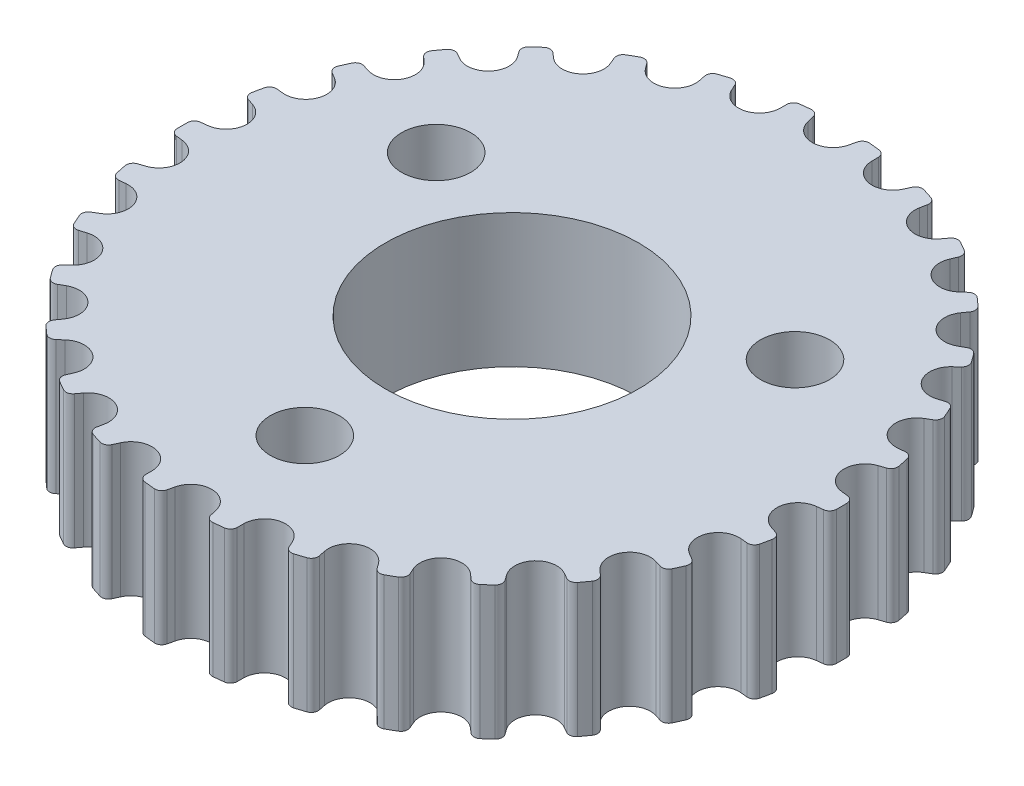
SolidWorks part; units mm, degrees
material "Acrylic (Medium-high impact)"
ref_plane "Front Plane" through (0, 0, 0) normal (0, 0, 1) x (1, 0, 0)
ref_plane "Top Plane" through (0, 0, 0) normal (0, 1, 0) x (1, 0, 0)
ref_plane "Right Plane" through (0, 0, 0) normal (1, 0, 0) x (0, 0, -1)
sketch "Sketch1" plane through (0, 0, 0) normal (0, 1, 0) x (1, 0, 0)
  circle A0 centre (0, 0) radius 14.3239
  dimension "D1" = 28.6479
extrude "Boss-Extrude1" add sketch "Sketch1" along normal blind 5.8
sketch "Sketch2" plane through (0, 5.8, 0) normal (0, 1, 0) x (1, 0, 0)
  line L0 (0, 0) -> (0, 14.3239) construction
  line L1 (-0.8883, 13.7564) -> (-0.95, 14.0339)
  line L2 (-2.9781, 14.0109) -> (-2.9781, 14.3239)
  line L3 (-2.9781, 14.3239) -> (2.9781, 14.3239)
  line L4 (0.8883, 13.7564) -> (0.95, 14.0339)
  line L5 (2.9781, 14.0109) -> (2.9781, 14.3239)
  circle A0 centre (0, 0) radius 14.3239 construction
  arc A1 (0.8883, 13.7564) -> (-0.8883, 13.7564) centre (0, 13.9539) cw
  arc A2 (-0.95, 14.0339) -> (-1.2694, 14.2676) centre (-1.2428, 13.9688) ccw
  arc A4 (0.95, 14.0339) -> (1.2694, 14.2676) centre (1.2428, 13.9688) cw
  arc A5 (-1.2694, 14.2676) -> (-2.9781, 14.0109) centre (0, 0) ccw
  arc A6 (1.2694, 14.2676) -> (2.9781, 14.0109) centre (0, 0) cw
  circle A8 centre (0, 0) radius 14.3239 construction
  point P11 (0, 14.3239)
  point P19 (0, 13.0439)
  dimension "D3" = 0.3
  dimension "D5" = 0.91
  dimension "D2" = 0.95
  dimension "D4" = 1.28
  dimension "D6" = 12
extrude "Cut-Extrude1" cut sketch "Sketch2" against normal through all
pattern_circular "CirPattern1" count 30 over 360 about axis through (0, 5.8, 0) along (0, -1, 0) of "Cut-Extrude1"
sketch "Sketch3" plane through (0, 0, 0) normal (0, -1, 0) x (1, 0, 0)
  circle A0 centre (0, 0) radius 5.5
  dimension "D1" = 11
extrude "Cut-Extrude2" cut sketch "Sketch3" against normal through all
sketch "Sketch4" plane through (0, 0, 0) normal (0, -1, 0) x (1, 0, 0)
  line L0 (0, 0) -> (0, 9) construction
  circle A0 centre (0, 9) radius 1.5
  circle A1 centre (7.7942, -4.5) radius 1.5
  circle A2 centre (-7.7942, -4.5) radius 1.5
  point P14 (0, 0)
  dimension "D1" = 3
  dimension "D2" = 9
  dimension "D3" = 3
extrude "Cut-Extrude3" cut sketch "Sketch4" against normal through all
sketch "Sketch5" plane through (0, 0, 0) normal (0, -1, 0) x (1, 0, 0)
  line L60 (8.7383, -10.682) -> (8.9513, -10.8702)
  line L61 (8.7383, -10.682) -> (8.9513, -10.8702)
  line L62 (9.875, -10.0385) -> (9.7101, -9.807)
  line L63 (9.875, -10.0385) -> (9.7101, -9.807)
  line L64 (12.5987, 6.2896) -> (12.3276, 6.2043)
  line L65 (12.5987, 6.2896) -> (12.3276, 6.2043)
  line L66 (11.5369, 7.5738) -> (11.7463, 7.766)
  line L67 (11.5369, 7.5738) -> (11.7463, 7.766)
  line L68 (-3.638, 13.3126) -> (-3.7561, 13.5712)
  line L69 (-3.638, 13.3126) -> (-3.7561, 13.5712)
  line L70 (-4.9382, 13.1871) -> (-4.8817, 12.9085)
  line L71 (-4.9382, 13.1871) -> (-4.8817, 12.9085)
  line L72 (-11.7463, 7.766) -> (-11.5369, 7.5738)
  line L73 (-11.7463, 7.766) -> (-11.5369, 7.5738)
  line L74 (-12.3276, 6.2043) -> (-12.5987, 6.2896)
  line L75 (-12.3276, 6.2043) -> (-12.5987, 6.2896)
  line L76 (-13.1043, 5.1541) -> (-12.8594, 5.0097)
  line L77 (-13.1043, 5.1541) -> (-12.8594, 5.0097)
  line L78 (-13.3481, 3.5057) -> (-13.6311, 3.5327)
  line L79 (-13.3481, 3.5057) -> (-13.6311, 3.5327)
  line L80 (-13.8895, 2.3169) -> (-13.62, 2.2266)
  line L81 (-13.8895, 2.3169) -> (-13.62, 2.2266)
  line L82 (-13.7853, 0.6538) -> (-14.0677, 0.6215)
  line L83 (-13.7853, 0.6538) -> (-14.0677, 0.6215)
  line L84 (-14.0677, -0.6215) -> (-13.7853, -0.6538)
  line L85 (-14.0677, -0.6215) -> (-13.7853, -0.6538)
  line L86 (-13.62, -2.2266) -> (-13.8895, -2.3169)
  line L87 (-13.62, -2.2266) -> (-13.8895, -2.3169)
  line L88 (-13.6311, -3.5327) -> (-13.3481, -3.5057)
  line L89 (-13.6311, -3.5327) -> (-13.3481, -3.5057)
  line L90 (-12.8594, -5.0097) -> (-13.1043, -5.1541)
  line L91 (-12.8594, -5.0097) -> (-13.1043, -5.1541)
  line L92 (-12.5987, -6.2896) -> (-12.3276, -6.2043)
  line L93 (-12.5987, -6.2896) -> (-12.3276, -6.2043)
  line L94 (-11.5369, -7.5738) -> (-11.7463, -7.766)
  line L95 (-11.5369, -7.5738) -> (-11.7463, -7.766)
  line L96 (-11.0157, -8.7716) -> (-10.7682, -8.6318)
  line L97 (-11.0157, -8.7716) -> (-10.7682, -8.6318)
  line L98 (-9.7101, -9.807) -> (-9.875, -10.0385)
  line L99 (-9.7101, -9.807) -> (-9.875, -10.0385)
  line L100 (-8.9513, -10.8702) -> (-8.7383, -10.682)
  line L101 (-8.9513, -10.8702) -> (-8.7383, -10.682)
  line L102 (-7.4589, -11.6115) -> (-7.5721, -11.8722)
  line L103 (-7.4589, -11.6115) -> (-7.5721, -11.8722)
  line L104 (-6.4956, -12.4937) -> (-6.3264, -12.2653)
  line L105 (-6.4956, -12.4937) -> (-6.3264, -12.2653)
  line L106 (-4.8817, -12.9085) -> (-4.9382, -13.1871)
  line L107 (-4.8817, -12.9085) -> (-4.9382, -13.1871)
  line L108 (-3.7561, -13.5712) -> (-3.638, -13.3126)
  line L109 (-3.7561, -13.5712) -> (-3.638, -13.3126)
  line L110 (-2.0912, -13.6414) -> (-2.0886, -13.9257)
  line L111 (-2.0912, -13.6414) -> (-2.0886, -13.9257)
  line L120 (6.3264, -12.2653) -> (6.4956, -12.4937)
  line L121 (7.5721, -11.8722) -> (7.4589, -11.6115)
  line L124 (10.7682, -8.6318) -> (11.0157, -8.7716)
  line L125 (11.7463, -7.766) -> (11.5369, -7.5738)
  line L126 (12.3276, -6.2043) -> (12.5987, -6.2896)
  line L127 (13.1043, -5.1541) -> (12.8594, -5.0097)
  line L128 (13.3481, -3.5057) -> (13.6311, -3.5327)
  line L129 (13.8895, -2.3169) -> (13.62, -2.2266)
  line L130 (13.7853, -0.6538) -> (14.0677, -0.6215)
  line L131 (14.0677, 0.6215) -> (13.7853, 0.6538)
  line L132 (13.62, 2.2266) -> (13.8895, 2.3169)
  line L133 (13.6311, 3.5327) -> (13.3481, 3.5057)
  line L134 (12.8594, 5.0097) -> (13.1043, 5.1541)
  line L137 (11.0157, 8.7716) -> (10.7682, 8.6318)
  line L138 (9.7101, 9.807) -> (9.875, 10.0385)
  line L139 (8.9513, 10.8702) -> (8.7383, 10.682)
  line L140 (7.4589, 11.6115) -> (7.5721, 11.8722)
  line L141 (6.4956, 12.4937) -> (6.3264, 12.2653)
  line L142 (4.8817, 12.9085) -> (4.9382, 13.1871)
  line L143 (3.7561, 13.5712) -> (3.638, 13.3126)
  line L144 (2.0912, 13.6414) -> (2.0886, 13.9257)
  line L145 (0.8524, 14.0556) -> (0.7907, 13.7781)
  line L146 (-0.7907, 13.7781) -> (-0.8524, 14.0556)
  line L147 (-2.0886, 13.9257) -> (-2.0912, 13.6414)
  line L150 (-6.3264, 12.2653) -> (-6.4956, 12.4937)
  line L151 (-7.5721, 11.8722) -> (-7.4589, 11.6115)
  line L152 (-8.7383, 10.682) -> (-8.9513, 10.8702)
  line L153 (-9.875, 10.0385) -> (-9.7101, 9.807)
  line L154 (-10.7682, 8.6318) -> (-11.0157, 8.7716)
  line L175 (-0.8524, -14.0556) -> (-0.7907, -13.7781)
  line L176 (0.7907, -13.7781) -> (0.8524, -14.0556)
  line L177 (2.0886, -13.9257) -> (2.0912, -13.6414)
  line L178 (3.638, -13.3126) -> (3.7561, -13.5712)
  line L179 (4.9382, -13.1871) -> (4.8817, -12.9085)
  line L180 (6.3264, -12.2653) -> (6.4956, -12.4937)
  line L181 (7.5721, -11.8722) -> (7.4589, -11.6115)
  line L184 (10.7682, -8.6318) -> (11.0157, -8.7716)
  line L185 (11.7463, -7.766) -> (11.5369, -7.5738)
  line L186 (12.3276, -6.2043) -> (12.5987, -6.2896)
  line L187 (13.1043, -5.1541) -> (12.8594, -5.0097)
  line L188 (13.3481, -3.5057) -> (13.6311, -3.5327)
  line L189 (13.8895, -2.3169) -> (13.62, -2.2266)
  line L190 (13.7853, -0.6538) -> (14.0677, -0.6215)
  line L191 (14.0677, 0.6215) -> (13.7853, 0.6538)
  line L192 (13.62, 2.2266) -> (13.8895, 2.3169)
  line L193 (13.6311, 3.5327) -> (13.3481, 3.5057)
  line L194 (12.8594, 5.0097) -> (13.1043, 5.1541)
  line L197 (11.0157, 8.7716) -> (10.7682, 8.6318)
  line L198 (9.7101, 9.807) -> (9.875, 10.0385)
  line L199 (8.9513, 10.8702) -> (8.7383, 10.682)
  line L200 (7.4589, 11.6115) -> (7.5721, 11.8722)
  line L201 (6.4956, 12.4937) -> (6.3264, 12.2653)
  line L202 (4.8817, 12.9085) -> (4.9382, 13.1871)
  line L203 (3.7561, 13.5712) -> (3.638, 13.3126)
  line L204 (2.0912, 13.6414) -> (2.0886, 13.9257)
  line L205 (0.8524, 14.0556) -> (0.7907, 13.7781)
  line L206 (-0.7907, 13.7781) -> (-0.8524, 14.0556)
  line L207 (-2.0886, 13.9257) -> (-2.0912, 13.6414)
  line L210 (-6.3264, 12.2653) -> (-6.4956, 12.4937)
  line L211 (-7.5721, 11.8722) -> (-7.4589, 11.6115)
  line L212 (-8.7383, 10.682) -> (-8.9513, 10.8702)
  line L213 (-9.875, 10.0385) -> (-9.7101, 9.807)
  line L214 (-10.7682, 8.6318) -> (-11.0157, 8.7716)
  line L235 (-0.8524, -14.0556) -> (-0.7907, -13.7781)
  line L236 (0.7907, -13.7781) -> (0.8524, -14.0556)
  line L237 (2.0886, -13.9257) -> (2.0912, -13.6414)
  line L238 (3.638, -13.3126) -> (3.7561, -13.5712)
  line L239 (4.9382, -13.1871) -> (4.8817, -12.9085)
  arc A76 (8.9513, -10.8702) -> (9.479, -10.8719) centre (9.2161, -10.5704) ccw
  arc A77 (8.9513, -10.8702) -> (9.479, -10.8719) centre (9.2161, -10.5704) ccw
  arc A78 (9.479, -10.8719) -> (9.8216, -10.5635) centre (0, 0) ccw
  arc A79 (9.479, -10.8719) -> (9.8216, -10.5635) centre (0, 0) ccw
  arc A80 (9.8216, -10.5635) -> (9.875, -10.0385) centre (9.5492, -10.2705) ccw
  arc A81 (9.8216, -10.5635) -> (9.875, -10.0385) centre (9.5492, -10.2705) ccw
  circle A120 centre (0, 0) radius 13.0439
  arc A121 (-0.8883, 13.7564) -> (0.8883, 13.7564) centre (0, 13.9539) ccw construction
  arc A128 (11.5369, 7.5738) -> (12.3276, 6.2043) centre (12.0845, 6.977) ccw
  arc A129 (11.5369, 7.5738) -> (12.3276, 6.2043) centre (12.0845, 6.977) ccw
  arc A130 (-3.7561, 13.5712) -> (-4.2375, 13.7875) centre (-4.12, 13.4051) ccw
  arc A131 (-3.7561, 13.5712) -> (-4.2375, 13.7875) centre (-4.12, 13.4051) ccw
  arc A132 (-4.2375, 13.7875) -> (-4.6759, 13.645) centre (0, 0) ccw
  arc A133 (-4.2375, 13.7875) -> (-4.6759, 13.645) centre (0, 0) ccw
  arc A134 (-4.6759, 13.645) -> (-4.9382, 13.1871) centre (-4.5462, 13.2666) ccw
  arc A135 (-4.6759, 13.645) -> (-4.9382, 13.1871) centre (-4.5462, 13.2666) ccw
  arc A136 (-11.8032, 8.2906) -> (-11.7463, 7.766) centre (-11.4759, 8.0607) ccw
  arc A137 (-11.8032, 8.2906) -> (-11.7463, 7.766) centre (-11.4759, 8.0607) ccw
  arc A138 (-12.3276, 6.2043) -> (-11.5369, 7.5738) centre (-12.0845, 6.977) ccw
  arc A139 (-12.3276, 6.2043) -> (-11.5369, 7.5738) centre (-12.0845, 6.977) ccw
  arc A140 (-12.5987, 6.2896) -> (-13.0815, 6.0766) centre (-12.7187, 5.908) ccw
  arc A141 (-12.5987, 6.2896) -> (-13.0815, 6.0766) centre (-12.7187, 5.908) ccw
  arc A142 (-13.0815, 6.0766) -> (-13.269, 5.6554) centre (0, 0) ccw
  arc A143 (-13.0815, 6.0766) -> (-13.269, 5.6554) centre (0, 0) ccw
  arc A144 (-13.269, 5.6554) -> (-13.1043, 5.1541) centre (-12.901, 5.4986) ccw
  arc A145 (-13.269, 5.6554) -> (-13.1043, 5.1541) centre (-12.901, 5.4986) ccw
  arc A146 (-13.3481, 3.5057) -> (-12.8594, 5.0097) centre (-13.271, 4.312) ccw
  arc A147 (-13.3481, 3.5057) -> (-12.8594, 5.0097) centre (-13.271, 4.312) ccw
  arc A148 (-13.6311, 3.5327) -> (-14.059, 3.224) centre (-13.6691, 3.1346) ccw
  arc A149 (-13.6311, 3.5327) -> (-14.059, 3.224) centre (-13.6691, 3.1346) ccw
  arc A150 (-14.059, 3.224) -> (-14.1549, 2.7731) centre (0, 0) ccw
  arc A151 (-14.059, 3.224) -> (-14.1549, 2.7731) centre (0, 0) ccw
  arc A152 (-14.1549, 2.7731) -> (-13.8895, 2.3169) centre (-13.7623, 2.6962) ccw
  arc A153 (-14.1549, 2.7731) -> (-13.8895, 2.3169) centre (-13.7623, 2.6962) ccw
  arc A154 (-13.7853, 0.6538) -> (-13.62, 2.2266) centre (-13.8775, 1.4586) ccw
  arc A155 (-13.7853, 0.6538) -> (-13.62, 2.2266) centre (-13.8775, 1.4586) ccw
  arc A156 (-14.0677, 0.6215) -> (-14.4221, 0.2305) centre (-14.0222, 0.2241) ccw
  arc A157 (-14.0677, 0.6215) -> (-14.4221, 0.2305) centre (-14.0222, 0.2241) ccw
  arc A158 (-14.4221, 0.2305) -> (-14.4221, -0.2305) centre (0, 0) ccw
  arc A159 (-14.4221, 0.2305) -> (-14.4221, -0.2305) centre (0, 0) ccw
  arc A160 (-14.4221, -0.2305) -> (-14.0677, -0.6215) centre (-14.0222, -0.2241) ccw
  arc A161 (-14.4221, -0.2305) -> (-14.0677, -0.6215) centre (-14.0222, -0.2241) ccw
  arc A162 (-13.62, -2.2266) -> (-13.7853, -0.6538) centre (-13.8775, -1.4586) ccw
  arc A163 (-13.62, -2.2266) -> (-13.7853, -0.6538) centre (-13.8775, -1.4586) ccw
  arc A164 (-13.8895, -2.3169) -> (-14.1549, -2.7731) centre (-13.7623, -2.6962) ccw
  arc A165 (-13.8895, -2.3169) -> (-14.1549, -2.7731) centre (-13.7623, -2.6962) ccw
  arc A166 (-14.1549, -2.7731) -> (-14.059, -3.224) centre (0, 0) ccw
  arc A167 (-14.1549, -2.7731) -> (-14.059, -3.224) centre (0, 0) ccw
  arc A168 (-14.059, -3.224) -> (-13.6311, -3.5327) centre (-13.6691, -3.1346) ccw
  arc A169 (-14.059, -3.224) -> (-13.6311, -3.5327) centre (-13.6691, -3.1346) ccw
  arc A170 (-12.8594, -5.0097) -> (-13.3481, -3.5057) centre (-13.271, -4.312) ccw
  arc A171 (-12.8594, -5.0097) -> (-13.3481, -3.5057) centre (-13.271, -4.312) ccw
  arc A172 (-13.1043, -5.1541) -> (-13.269, -5.6554) centre (-12.901, -5.4986) ccw
  arc A173 (-13.1043, -5.1541) -> (-13.269, -5.6554) centre (-12.901, -5.4986) ccw
  arc A174 (-13.269, -5.6554) -> (-13.0815, -6.0766) centre (0, 0) ccw
  arc A175 (-13.269, -5.6554) -> (-13.0815, -6.0766) centre (0, 0) ccw
  arc A176 (-13.0815, -6.0766) -> (-12.5987, -6.2896) centre (-12.7187, -5.908) ccw
  arc A177 (-13.0815, -6.0766) -> (-12.5987, -6.2896) centre (-12.7187, -5.908) ccw
  arc A178 (-11.5369, -7.5738) -> (-12.3276, -6.2043) centre (-12.0845, -6.977) ccw
  arc A179 (-11.5369, -7.5738) -> (-12.3276, -6.2043) centre (-12.0845, -6.977) ccw
  arc A180 (-11.7463, -7.766) -> (-11.8032, -8.2906) centre (-11.4759, -8.0607) ccw
  arc A181 (-11.7463, -7.766) -> (-11.8032, -8.2906) centre (-11.4759, -8.0607) ccw
  arc A182 (-11.8032, -8.2906) -> (-11.5323, -8.6636) centre (0, 0) ccw
  arc A183 (-11.8032, -8.2906) -> (-11.5323, -8.6636) centre (0, 0) ccw
  arc A184 (-11.5323, -8.6636) -> (-11.0157, -8.7716) centre (-11.2124, -8.4233) ccw
  arc A185 (-11.5323, -8.6636) -> (-11.0157, -8.7716) centre (-11.2124, -8.4233) ccw
  arc A186 (-9.7101, -9.807) -> (-10.7682, -8.6318) centre (-10.3698, -9.337) ccw
  arc A187 (-9.7101, -9.807) -> (-10.7682, -8.6318) centre (-10.3698, -9.337) ccw
  arc A188 (-9.875, -10.0385) -> (-9.8216, -10.5635) centre (-9.5492, -10.2705) ccw
  arc A189 (-9.875, -10.0385) -> (-9.8216, -10.5635) centre (-9.5492, -10.2705) ccw
  arc A190 (-9.8216, -10.5635) -> (-9.479, -10.8719) centre (0, 0) ccw
  arc A191 (-9.8216, -10.5635) -> (-9.479, -10.8719) centre (0, 0) ccw
  arc A192 (-9.479, -10.8719) -> (-8.9513, -10.8702) centre (-9.2161, -10.5704) ccw
  arc A193 (-9.479, -10.8719) -> (-8.9513, -10.8702) centre (-9.2161, -10.5704) ccw
  arc A194 (-7.4589, -11.6115) -> (-8.7383, -10.682) centre (-8.2019, -11.289) ccw
  arc A195 (-7.4589, -11.6115) -> (-8.7383, -10.682) centre (-8.2019, -11.289) ccw
  arc A196 (-7.5721, -11.8722) -> (-7.4107, -12.3747) centre (-7.2051, -12.0315) ccw
  arc A197 (-7.5721, -11.8722) -> (-7.4107, -12.3747) centre (-7.2051, -12.0315) ccw
  arc A198 (-7.4107, -12.3747) -> (-7.0114, -12.6052) centre (0, 0) ccw
  arc A199 (-7.4107, -12.3747) -> (-7.0114, -12.6052) centre (0, 0) ccw
  arc A200 (-7.0114, -12.6052) -> (-6.4956, -12.4937) centre (-6.817, -12.2556) ccw
  arc A201 (-7.0114, -12.6052) -> (-6.4956, -12.4937) centre (-6.817, -12.2556) ccw
  arc A202 (-4.8817, -12.9085) -> (-6.3264, -12.2653) centre (-5.6756, -12.7476) ccw
  arc A203 (-4.8817, -12.9085) -> (-6.3264, -12.2653) centre (-5.6756, -12.7476) ccw
  arc A204 (-4.9382, -13.1871) -> (-4.6759, -13.645) centre (-4.5462, -13.2666) ccw
  arc A205 (-4.9382, -13.1871) -> (-4.6759, -13.645) centre (-4.5462, -13.2666) ccw
  arc A206 (-4.6759, -13.645) -> (-4.2375, -13.7875) centre (0, 0) ccw
  arc A207 (-4.6759, -13.645) -> (-4.2375, -13.7875) centre (0, 0) ccw
  arc A208 (-4.2375, -13.7875) -> (-3.7561, -13.5712) centre (-4.12, -13.4051) ccw
  arc A209 (-4.2375, -13.7875) -> (-3.7561, -13.5712) centre (-4.12, -13.4051) ccw
  arc A210 (-2.0912, -13.6414) -> (-3.638, -13.3126) centre (-2.9012, -13.649) ccw
  arc A211 (-2.0912, -13.6414) -> (-3.638, -13.3126) centre (-2.9012, -13.649) ccw
  arc A212 (-2.0886, -13.9257) -> (-1.7367, -14.319) centre (-1.6886, -13.9219) ccw
  arc A213 (-2.0886, -13.9257) -> (-1.7367, -14.319) centre (-1.6886, -13.9219) ccw
  arc A214 (-1.7367, -14.319) -> (-1.2783, -14.3672) centre (0, 0) ccw
  arc A215 (-1.7367, -14.319) -> (-1.2783, -14.3672) centre (0, 0) ccw
  arc A240 (6.4956, -12.4937) -> (7.0114, -12.6052) centre (6.817, -12.2556) ccw
  arc A241 (7.0114, -12.6052) -> (7.4107, -12.3747) centre (0, 0) ccw
  arc A242 (7.4107, -12.3747) -> (7.5721, -11.8722) centre (7.2051, -12.0315) ccw
  arc A243 (8.7383, -10.682) -> (7.4589, -11.6115) centre (8.2019, -11.289) ccw
  arc A247 (10.7682, -8.6318) -> (9.7101, -9.807) centre (10.3698, -9.337) ccw
  arc A248 (11.0157, -8.7716) -> (11.5323, -8.6636) centre (11.2124, -8.4233) ccw
  arc A249 (11.5323, -8.6636) -> (11.8032, -8.2906) centre (0, 0) ccw
  arc A250 (11.8032, -8.2906) -> (11.7463, -7.766) centre (11.4759, -8.0607) ccw
  arc A251 (12.3276, -6.2043) -> (11.5369, -7.5738) centre (12.0845, -6.977) ccw
  arc A252 (12.5987, -6.2896) -> (13.0815, -6.0766) centre (12.7187, -5.908) ccw
  arc A253 (13.0815, -6.0766) -> (13.269, -5.6554) centre (0, 0) ccw
  arc A254 (13.269, -5.6554) -> (13.1043, -5.1541) centre (12.901, -5.4986) ccw
  arc A255 (13.3481, -3.5057) -> (12.8594, -5.0097) centre (13.271, -4.312) ccw
  arc A256 (13.6311, -3.5327) -> (14.059, -3.224) centre (13.6691, -3.1346) ccw
  arc A257 (14.059, -3.224) -> (14.1549, -2.7731) centre (0, 0) ccw
  arc A258 (14.1549, -2.7731) -> (13.8895, -2.3169) centre (13.7623, -2.6962) ccw
  arc A259 (13.7853, -0.6538) -> (13.62, -2.2266) centre (13.8775, -1.4586) ccw
  arc A260 (14.0677, -0.6215) -> (14.4221, -0.2305) centre (14.0222, -0.2241) ccw
  arc A261 (14.4221, -0.2305) -> (14.4221, 0.2305) centre (0, 0) ccw
  arc A262 (14.4221, 0.2305) -> (14.0677, 0.6215) centre (14.0222, 0.2241) ccw
  arc A263 (13.62, 2.2266) -> (13.7853, 0.6538) centre (13.8775, 1.4586) ccw
  arc A264 (13.8895, 2.3169) -> (14.1549, 2.7731) centre (13.7623, 2.6962) ccw
  arc A265 (14.1549, 2.7731) -> (14.059, 3.224) centre (0, 0) ccw
  arc A266 (14.059, 3.224) -> (13.6311, 3.5327) centre (13.6691, 3.1346) ccw
  arc A267 (12.8594, 5.0097) -> (13.3481, 3.5057) centre (13.271, 4.312) ccw
  arc A268 (13.1043, 5.1541) -> (13.269, 5.6554) centre (12.901, 5.4986) ccw
  arc A269 (13.269, 5.6554) -> (13.0815, 6.0766) centre (0, 0) ccw
  arc A270 (13.0815, 6.0766) -> (12.5987, 6.2896) centre (12.7187, 5.908) ccw
  arc A272 (11.7463, 7.766) -> (11.8032, 8.2906) centre (11.4759, 8.0607) ccw
  arc A273 (11.8032, 8.2906) -> (11.5323, 8.6636) centre (0, 0) ccw
  arc A274 (11.5323, 8.6636) -> (11.0157, 8.7716) centre (11.2124, 8.4233) ccw
  arc A275 (9.7101, 9.807) -> (10.7682, 8.6318) centre (10.3698, 9.337) ccw
  arc A276 (9.875, 10.0385) -> (9.8216, 10.5635) centre (9.5492, 10.2705) ccw
  arc A277 (9.8216, 10.5635) -> (9.479, 10.8719) centre (0, 0) ccw
  arc A278 (9.479, 10.8719) -> (8.9513, 10.8702) centre (9.2161, 10.5704) ccw
  arc A279 (7.4589, 11.6115) -> (8.7383, 10.682) centre (8.2019, 11.289) ccw
  arc A280 (7.5721, 11.8722) -> (7.4107, 12.3747) centre (7.2051, 12.0315) ccw
  arc A281 (7.4107, 12.3747) -> (7.0114, 12.6052) centre (0, 0) ccw
  arc A282 (7.0114, 12.6052) -> (6.4956, 12.4937) centre (6.817, 12.2556) ccw
  arc A283 (4.8817, 12.9085) -> (6.3264, 12.2653) centre (5.6756, 12.7476) ccw
  arc A284 (4.9382, 13.1871) -> (4.6759, 13.645) centre (4.5462, 13.2666) ccw
  arc A285 (4.6759, 13.645) -> (4.2375, 13.7875) centre (0, 0) ccw
  arc A286 (4.2375, 13.7875) -> (3.7561, 13.5712) centre (4.12, 13.4051) ccw
  arc A287 (2.0912, 13.6414) -> (3.638, 13.3126) centre (2.9012, 13.649) ccw
  arc A288 (2.0886, 13.9257) -> (1.7367, 14.319) centre (1.6886, 13.9219) ccw
  arc A289 (1.7367, 14.319) -> (1.2783, 14.3672) centre (0, 0) ccw
  arc A290 (1.2783, 14.3672) -> (0.8524, 14.0556) centre (1.2428, 13.9688) ccw
  arc A291 (-0.7907, 13.7781) -> (0.7907, 13.7781) centre (0, 13.9539) ccw
  arc A292 (-0.8524, 14.0556) -> (-1.2783, 14.3672) centre (-1.2428, 13.9688) ccw
  arc A293 (-1.2783, 14.3672) -> (-1.7367, 14.319) centre (0, 0) ccw
  arc A294 (-1.7367, 14.319) -> (-2.0886, 13.9257) centre (-1.6886, 13.9219) ccw
  arc A295 (-3.638, 13.3126) -> (-2.0912, 13.6414) centre (-2.9012, 13.649) ccw
  arc A299 (-6.3264, 12.2653) -> (-4.8817, 12.9085) centre (-5.6756, 12.7476) ccw
  arc A300 (-6.4956, 12.4937) -> (-7.0114, 12.6052) centre (-6.817, 12.2556) ccw
  arc A301 (-7.0114, 12.6052) -> (-7.4107, 12.3747) centre (0, 0) ccw
  arc A302 (-7.4107, 12.3747) -> (-7.5721, 11.8722) centre (-7.2051, 12.0315) ccw
  arc A303 (-8.7383, 10.682) -> (-7.4589, 11.6115) centre (-8.2019, 11.289) ccw
  arc A304 (-8.9513, 10.8702) -> (-9.479, 10.8719) centre (-9.2161, 10.5704) ccw
  arc A305 (-9.479, 10.8719) -> (-9.8216, 10.5635) centre (0, 0) ccw
  arc A306 (-9.8216, 10.5635) -> (-9.875, 10.0385) centre (-9.5492, 10.2705) ccw
  arc A307 (-10.7682, 8.6318) -> (-9.7101, 9.807) centre (-10.3698, 9.337) ccw
  arc A308 (-11.0157, 8.7716) -> (-11.5323, 8.6636) centre (-11.2124, 8.4233) ccw
  arc A309 (-11.5323, 8.6636) -> (-11.8032, 8.2906) centre (0, 0) ccw
  arc A350 (-1.2783, -14.3672) -> (-0.8524, -14.0556) centre (-1.2428, -13.9688) ccw
  arc A351 (0.7907, -13.7781) -> (-0.7907, -13.7781) centre (0, -13.9539) ccw
  arc A352 (0.8524, -14.0556) -> (1.2783, -14.3672) centre (1.2428, -13.9688) ccw
  arc A353 (1.2783, -14.3672) -> (1.7367, -14.319) centre (0, 0) ccw
  arc A354 (1.7367, -14.319) -> (2.0886, -13.9257) centre (1.6886, -13.9219) ccw
  arc A355 (3.638, -13.3126) -> (2.0912, -13.6414) centre (2.9012, -13.649) ccw
  arc A356 (3.7561, -13.5712) -> (4.2375, -13.7875) centre (4.12, -13.4051) ccw
  arc A357 (4.2375, -13.7875) -> (4.6759, -13.645) centre (0, 0) ccw
  arc A358 (4.6759, -13.645) -> (4.9382, -13.1871) centre (4.5462, -13.2666) ccw
  arc A359 (6.3264, -12.2653) -> (4.8817, -12.9085) centre (5.6756, -12.7476) ccw
  arc A360 (6.4956, -12.4937) -> (7.0114, -12.6052) centre (6.817, -12.2556) ccw
  arc A361 (7.0114, -12.6052) -> (7.4107, -12.3747) centre (0, 0) ccw
  arc A362 (7.4107, -12.3747) -> (7.5721, -11.8722) centre (7.2051, -12.0315) ccw
  arc A363 (8.7383, -10.682) -> (7.4589, -11.6115) centre (8.2019, -11.289) ccw
  arc A367 (10.7682, -8.6318) -> (9.7101, -9.807) centre (10.3698, -9.337) ccw
  arc A368 (11.0157, -8.7716) -> (11.5323, -8.6636) centre (11.2124, -8.4233) ccw
  arc A369 (11.5323, -8.6636) -> (11.8032, -8.2906) centre (0, 0) ccw
  arc A370 (11.8032, -8.2906) -> (11.7463, -7.766) centre (11.4759, -8.0607) ccw
  arc A371 (12.3276, -6.2043) -> (11.5369, -7.5738) centre (12.0845, -6.977) ccw
  arc A372 (12.5987, -6.2896) -> (13.0815, -6.0766) centre (12.7187, -5.908) ccw
  arc A373 (13.0815, -6.0766) -> (13.269, -5.6554) centre (0, 0) ccw
  arc A374 (13.269, -5.6554) -> (13.1043, -5.1541) centre (12.901, -5.4986) ccw
  arc A375 (13.3481, -3.5057) -> (12.8594, -5.0097) centre (13.271, -4.312) ccw
  arc A376 (13.6311, -3.5327) -> (14.059, -3.224) centre (13.6691, -3.1346) ccw
  arc A377 (14.059, -3.224) -> (14.1549, -2.7731) centre (0, 0) ccw
  arc A378 (14.1549, -2.7731) -> (13.8895, -2.3169) centre (13.7623, -2.6962) ccw
  arc A379 (13.7853, -0.6538) -> (13.62, -2.2266) centre (13.8775, -1.4586) ccw
  arc A380 (14.0677, -0.6215) -> (14.4221, -0.2305) centre (14.0222, -0.2241) ccw
  arc A381 (14.4221, -0.2305) -> (14.4221, 0.2305) centre (0, 0) ccw
  arc A382 (14.4221, 0.2305) -> (14.0677, 0.6215) centre (14.0222, 0.2241) ccw
  arc A383 (13.62, 2.2266) -> (13.7853, 0.6538) centre (13.8775, 1.4586) ccw
  arc A384 (13.8895, 2.3169) -> (14.1549, 2.7731) centre (13.7623, 2.6962) ccw
  arc A385 (14.1549, 2.7731) -> (14.059, 3.224) centre (0, 0) ccw
  arc A386 (14.059, 3.224) -> (13.6311, 3.5327) centre (13.6691, 3.1346) ccw
  arc A387 (12.8594, 5.0097) -> (13.3481, 3.5057) centre (13.271, 4.312) ccw
  arc A388 (13.1043, 5.1541) -> (13.269, 5.6554) centre (12.901, 5.4986) ccw
  arc A389 (13.269, 5.6554) -> (13.0815, 6.0766) centre (0, 0) ccw
  arc A390 (13.0815, 6.0766) -> (12.5987, 6.2896) centre (12.7187, 5.908) ccw
  arc A392 (11.7463, 7.766) -> (11.8032, 8.2906) centre (11.4759, 8.0607) ccw
  arc A393 (11.8032, 8.2906) -> (11.5323, 8.6636) centre (0, 0) ccw
  arc A394 (11.5323, 8.6636) -> (11.0157, 8.7716) centre (11.2124, 8.4233) ccw
  arc A395 (9.7101, 9.807) -> (10.7682, 8.6318) centre (10.3698, 9.337) ccw
  arc A396 (9.875, 10.0385) -> (9.8216, 10.5635) centre (9.5492, 10.2705) ccw
  arc A397 (9.8216, 10.5635) -> (9.479, 10.8719) centre (0, 0) ccw
  arc A398 (9.479, 10.8719) -> (8.9513, 10.8702) centre (9.2161, 10.5704) ccw
  arc A399 (7.4589, 11.6115) -> (8.7383, 10.682) centre (8.2019, 11.289) ccw
  arc A400 (7.5721, 11.8722) -> (7.4107, 12.3747) centre (7.2051, 12.0315) ccw
  arc A401 (7.4107, 12.3747) -> (7.0114, 12.6052) centre (0, 0) ccw
  arc A402 (7.0114, 12.6052) -> (6.4956, 12.4937) centre (6.817, 12.2556) ccw
  arc A403 (4.8817, 12.9085) -> (6.3264, 12.2653) centre (5.6756, 12.7476) ccw
  arc A404 (4.9382, 13.1871) -> (4.6759, 13.645) centre (4.5462, 13.2666) ccw
  arc A405 (4.6759, 13.645) -> (4.2375, 13.7875) centre (0, 0) ccw
  arc A406 (4.2375, 13.7875) -> (3.7561, 13.5712) centre (4.12, 13.4051) ccw
  arc A407 (2.0912, 13.6414) -> (3.638, 13.3126) centre (2.9012, 13.649) ccw
  arc A408 (2.0886, 13.9257) -> (1.7367, 14.319) centre (1.6886, 13.9219) ccw
  arc A409 (1.7367, 14.319) -> (1.2783, 14.3672) centre (0, 0) ccw
  arc A410 (1.2783, 14.3672) -> (0.8524, 14.0556) centre (1.2428, 13.9688) ccw
  arc A411 (-0.7907, 13.7781) -> (0.7907, 13.7781) centre (0, 13.9539) ccw
  arc A412 (-0.8524, 14.0556) -> (-1.2783, 14.3672) centre (-1.2428, 13.9688) ccw
  arc A413 (-1.2783, 14.3672) -> (-1.7367, 14.319) centre (0, 0) ccw
  arc A414 (-1.7367, 14.319) -> (-2.0886, 13.9257) centre (-1.6886, 13.9219) ccw
  arc A415 (-3.638, 13.3126) -> (-2.0912, 13.6414) centre (-2.9012, 13.649) ccw
  arc A419 (-6.3264, 12.2653) -> (-4.8817, 12.9085) centre (-5.6756, 12.7476) ccw
  arc A420 (-6.4956, 12.4937) -> (-7.0114, 12.6052) centre (-6.817, 12.2556) ccw
  arc A421 (-7.0114, 12.6052) -> (-7.4107, 12.3747) centre (0, 0) ccw
  arc A422 (-7.4107, 12.3747) -> (-7.5721, 11.8722) centre (-7.2051, 12.0315) ccw
  arc A423 (-8.7383, 10.682) -> (-7.4589, 11.6115) centre (-8.2019, 11.289) ccw
  arc A424 (-8.9513, 10.8702) -> (-9.479, 10.8719) centre (-9.2161, 10.5704) ccw
  arc A425 (-9.479, 10.8719) -> (-9.8216, 10.5635) centre (0, 0) ccw
  arc A426 (-9.8216, 10.5635) -> (-9.875, 10.0385) centre (-9.5492, 10.2705) ccw
  arc A427 (-10.7682, 8.6318) -> (-9.7101, 9.807) centre (-10.3698, 9.337) ccw
  arc A428 (-11.0157, 8.7716) -> (-11.5323, 8.6636) centre (-11.2124, 8.4233) ccw
  arc A429 (-11.5323, 8.6636) -> (-11.8032, 8.2906) centre (0, 0) ccw
  arc A470 (-1.2783, -14.3672) -> (-0.8524, -14.0556) centre (-1.2428, -13.9688) ccw
  arc A471 (0.7907, -13.7781) -> (-0.7907, -13.7781) centre (0, -13.9539) ccw
  arc A472 (0.8524, -14.0556) -> (1.2783, -14.3672) centre (1.2428, -13.9688) ccw
  arc A473 (1.2783, -14.3672) -> (1.7367, -14.319) centre (0, 0) ccw
  arc A474 (1.7367, -14.319) -> (2.0886, -13.9257) centre (1.6886, -13.9219) ccw
  arc A475 (3.638, -13.3126) -> (2.0912, -13.6414) centre (2.9012, -13.649) ccw
  arc A476 (3.7561, -13.5712) -> (4.2375, -13.7875) centre (4.12, -13.4051) ccw
  arc A477 (4.2375, -13.7875) -> (4.6759, -13.645) centre (0, 0) ccw
  arc A478 (4.6759, -13.645) -> (4.9382, -13.1871) centre (4.5462, -13.2666) ccw
  arc A479 (6.3264, -12.2653) -> (4.8817, -12.9085) centre (5.6756, -12.7476) ccw
  dimension "D1" = 0.1
extrude "Boss-Extrude2" [suppressed] add sketch "Sketch5" against normal up to surface (5.8 mm away) up to face at (7.7942, 5.8, -6)
equation "\"smallPulleyTeeth\"= 15"
equation "\"largePulleyTeeth\"= 30"
equation "\"eighthThick\"= 2.9mm"
equation "\"D1@Sketch1\"=3*\"largePulleyTeeth\"/pi"
equation "\"D1@Boss-Extrude1\" = \"eighthThick\" * 2"
equation "\"D6@Sketch2\"=360/\"largePulleyTeeth\""
equation "\"quarterThick\"=6.0mm"
equation "\"D1@CirPattern1\"=\"largePulleyTeeth\""
equation "\"sixteenthThick\" = 1.7mm"
equation "\"OD\" = 145mm"
equation "\"puckAngle\" = 60.5deg"
equation "\"puckDiam\" = 76.5mm"
equation "\"axlePress\" = 5.9mm"
equation "\"press\" = 0.2mm"
equation "\"wheelClear\" = 0.3mm"
equation "\"10-32clear\" = 4.8mm"
equation "\"D1@Sketch4\"=\"4-40clear\""
equation "\"6-32clear\" = 3.3mm"
equation "\"8-32clear\" = 4.0mm"
equation "\"4-40clear\" = 3.0mm"
equation "\"wheelHeight\" = 22mm"
equation "\"wheelWell\" = 65mm"
